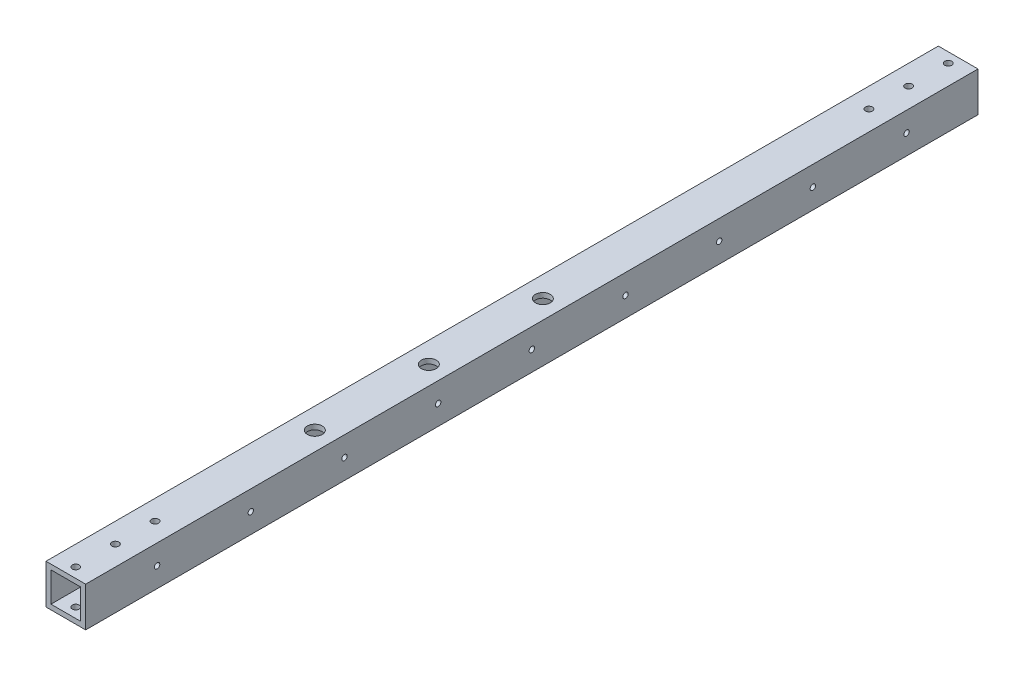
SolidWorks part; units mm, degrees
material "6061-T6 (SS)"
ref_plane "Front Plane" through (0, 0, 0) normal (0, 0, 1) x (1, 0, 0)
ref_plane "Top Plane" through (0, 0, 0) normal (0, 1, 0) x (1, 0, 0)
ref_plane "Right Plane" through (0, 0, 0) normal (1, 0, 0) x (0, 0, -1)
sketch "Sketch1" plane through (0, 0, 0) normal (0, 0, 1) x (1, 0, 0)
  line L1 (-12.7, -12.7) -> (12.7, -12.7)
  line L2 (-12.7, -12.7) -> (-12.7, 12.7)
  line L3 (-12.7, 12.7) -> (12.7, 12.7)
  line L4 (12.7, -12.7) -> (12.7, 12.7)
  line L5 (-12.7, -12.7) -> (12.7, 12.7) construction
  line L6 (-12.7, 12.7) -> (12.7, -12.7) construction
  point P0 (0, 0)
  dimension "D1" = 25.4
  dimension "D2" = 25.4
extrude "Extrude-Thin1" add sketch "Sketch1" along normal blind 571.5 thin thin type one direction reverse wall 3.175
hole_wizard "#8 Clearance Hole1" positions "3DSketch1" profile "Sketch3" hole size "#8" standard "ANSI Inch" end condition through all
sketch3d "3DSketch1"
  line L1 (12.7, 12.7, 0) -> (-12.7, 12.7, 0) construction
  line L6 (0, 12.7, 571.5) -> (0, 12.7, 0) construction
  line L7 (12.7, 12.7, 571.5) -> (-12.7, 12.7, 571.5) construction
  point P57 (0, 12.7, 6.35)
  point P59 (0, 12.7, 31.75)
  point P61 (0, 12.7, 57.15)
  point P63 (0, 12.7, 539.75)
  point P65 (0, 12.7, 514.35)
  point P67 (0, 12.7, 565.15)
  dimension "D1" = 25.4
  dimension "D2" = 25.4
  dimension "D3" = 6.35
  dimension "D4" = 25.4
  dimension "D5" = 25.4
  dimension "D6" = 6.35
sketch "Sketch3" plane through (0, 12.7, 565.15) normal (1, 0, 0) x (0, 0, 1)
  line L0 (0, 0) -> (0, 25.4)
  line L1 (0, 25.4) -> (2.2479, 25.4)
  line L2 (2.2479, 25.4) -> (2.2479, 0)
  line L5 (2.2479, 0) -> (0, 0)
  line L11 (0, -6.35) -> (0, 107.95) construction
  dimension "Thru Hole Dia." = 4.4958
  dimension "Thru Hole Depth" = 25.4
hole_wizard "#8-32 Tapped Hole1" positions "Sketch4" profile "Sketch5" tap size "#8-32" standard "ANSI Inch"
sketch "Sketch4" plane through (12.7, 82.55, 285.75) normal (1, 0, 0) x (0, 0, 1)
  point P0 (-300, 82.55)
  point P3 (-240, 82.55)
  point P6 (-180, 82.55)
  point P9 (-60, 82.55)
  point P12 (0, 82.55)
  point P15 (60, 82.55)
  point P18 (120, 82.55)
  point P21 (180, 82.55)
  point P24 (240, 82.55)
  point P27 (-120, 82.55)
  point P30 (-360, 82.55)
  point P33 (300, 82.55)
  point P36 (360, 82.55)
sketch "Sketch5" plane through (12.7, 0, -14.25) normal (0, 1, 0) x (0, 0, -1)
  line L0 (0, 0) -> (0, 11.7464)
  line L1 (0, 11.7464) -> (1.7272, 10.7086)
  line L2 (1.7272, 10.7086) -> (1.7272, 0)
  line L3 (1.7272, 0) -> (0, 0)
  line L4 (0, 11.7464) -> (-1.7272, 10.7086) construction
  line L5 (0, -6.35) -> (0, 107.95) construction
  dimension "Tap Drill Dia." = 3.4544
  dimension "Tap Drill Depth" = 10.7086
  dimension "Drill Angle" = 118
hole_wizard "3/8 (0.375) Diameter Hole2" positions "Sketch8" profile "Sketch9" hole size "3/8" standard "ANSI Inch" end condition through all
sketch "Sketch8" plane through (-346.075, -12.7, 285.75) normal (0, -1, 0) x (0, 0, 1)
  point P9 (-92.7735, 346.075)
  point P12 (-35.6235, 346.075)
  point P18 (35.6235, 346.075)
  point P21 (92.7735, 346.075)
  point P24 (-19.05, -346.775)
  point P27 (53.975, -346.775)
  point P30 (127, -346.775)
  point P42 (-381, -114.3)
  point P45 (-381, -130.175)
  point P48 (-381, -146.05)
  point P55 (-381, 114.3)
  point P58 (-381, 98.425)
  point P61 (-381, 82.55)
sketch "Sketch9" plane through (-692.15, -12.7, 192.9765) normal (1, 0, 0) x (0, 0, -1)
  line L0 (0, 0) -> (0, 25.4)
  line L1 (0, 25.4) -> (4.7625, 25.4)
  line L2 (4.7625, 25.4) -> (4.7625, 0)
  line L3 (4.7625, 0) -> (0, 0)
  line L4 (0, -6.35) -> (0, 107.95) construction
  dimension "Thru Hole Dia." = 9.525
  dimension "Thru Hole Depth" = 25.4
